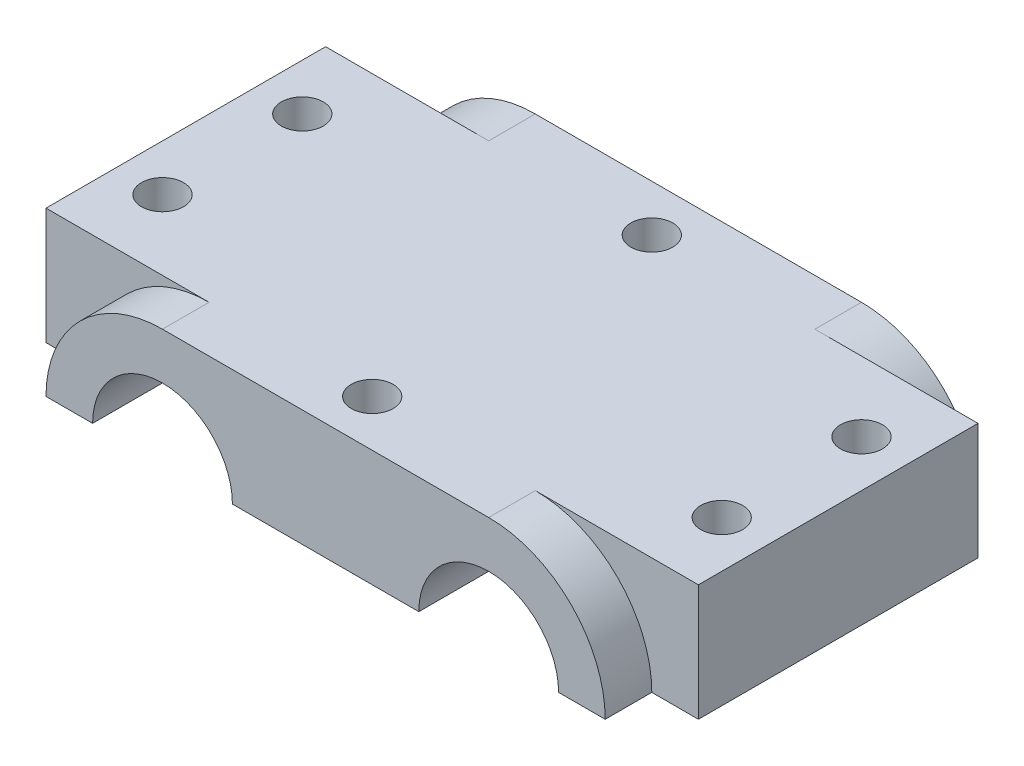
SolidWorks part; units mm, degrees
ref_plane "Front Plane" through (0, 0, 0) normal (0, 0, 1) x (1, 0, 0)
ref_plane "Top Plane" through (0, 0, 0) normal (0, 1, 0) x (1, 0, 0)
ref_plane "Right Plane" through (0, 0, 0) normal (1, 0, 0) x (0, 0, -1)
sketch "Sketch1" plane through (0, 0, 0) normal (0, 0, 1) x (1, 0, 0)
  line L0 (0, 0) -> (10, 0)
  line L2 (0, 0) -> (0, 12.5)
  line L4 (70, 0) -> (70, 12.5)
  line L10 (0, 0) -> (10, 0)
  line L11 (0, 12.5) -> (70, 12.5)
  line L12 (70, 0) -> (60, 0)
  line L13 (25, 0) -> (45, 0)
  line L14 (60, 0) -> (70, 0)
  arc A0 (17.5, 12.5) -> (5, 0) centre (17.5, 0) ccw
  arc A1 (65, 0) -> (52.5, 12.5) centre (52.5, 0) ccw
  arc A2 (25, 0) -> (10, 0) centre (17.5, 0) ccw
  arc A3 (60, 0) -> (45, 0) centre (52.5, 0) ccw
  dimension "D3" = 17.5
  dimension "D4" = 17.5
  dimension "D5" = 15
  dimension "D6" = 15
  dimension "D1" = 70
  dimension "D2" = 12.5
extrude "Boss-Extrude3" add sketch "Sketch1" along normal mid plane 30 contours A3 L14 A1 L11 A0 L10 A2 L13 | A0 L11 L2 L0 | A1 L12 L4 L11 region at (4.3479, 7.4574, 0) region at (35, 6.8625, 0) region at (65.6521, 7.4574, 0)
sketch "Sketch2" plane through (0, 12.5, 0) normal (0, 1, 0) x (1, 0, 0)
  circle A0 centre (35, -5) radius 2.25
  circle A1 centre (35, -35) radius 2.25
extrude "Cut-Extrude3" cut sketch "Sketch2" against normal through all
extrude "Boss-Extrude4" add sketch "Sketch1<9>" along normal mid plane 40 contours A3 L14 A1 L11 A0 L10 A2 L13 region at (35, 6.8625, 0)
sketch "Sketch1<9>" plane through (0, 0, 0) normal (0, 0, 1) x (1, 0, 0) same geometry as "Sketch1"
sketch "Sketch4" plane through (0, 12.5, 0) normal (0, 1, 0) x (1, 0, 0)
  line L0 (35, 20) -> (35, -20) construction
  line L1 (17.5, 20) -> (52.5, 20) construction
  line L2 (17.5, -20) -> (52.5, -20) construction
  line L3 (35, 0) -> (58.321, 0) construction
  line L4 (0, -15) -> (0, 15) construction
  circle A0 centre (35, 15) radius 2.25
  circle A1 centre (5, 7.5) radius 2.25
  circle A2 centre (65, 7.5) radius 2.25
  circle A3 centre (35, -15) radius 2.25
  circle A4 centre (65, -7.5) radius 2.25
  circle A5 centre (5, -7.5) radius 2.25
  dimension "D1" = 4.5
  dimension "D2" = 4.5
  dimension "D3" = 5
  dimension "D4" = 5
  dimension "D5" = 15
extrude "Cut-Extrude4" cut sketch "Sketch4" against normal through all both and the other way through all
